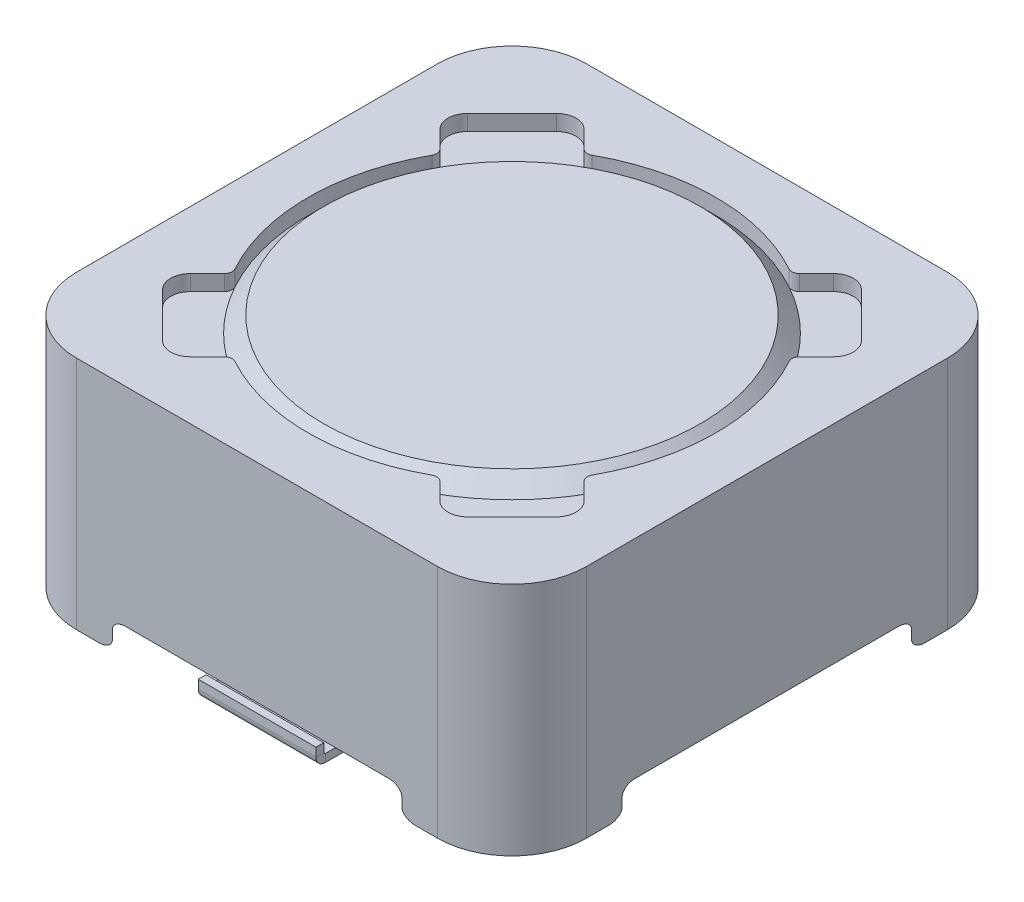
SolidWorks part; units mm, degrees
ref_plane "Front Plane" through (0, 0, 0) normal (0, 0, 1) x (1, 0, 0)
ref_plane "Top Plane" through (0, 0, 0) normal (0, 1, 0) x (1, 0, 0)
ref_plane "Right Plane" through (0, 0, 0) normal (1, 0, 0) x (0, 0, -1)
sketch "Sketch1" plane through (0, 0, 0) normal (0, 1, 0) x (1, 0, 0)
  line L1 (-2.3, 3.25) -> (2.3, 3.25)
  line L2 (-3.25, 2.3) -> (-3.25, -2.3)
  line L3 (-2.3, -3.25) -> (2.3, -3.25)
  line L4 (3.25, 2.3) -> (3.25, -2.3)
  line L5 (-3.25, 3.25) -> (3.25, -3.25) construction
  line L6 (-3.25, -3.25) -> (3.25, 3.25) construction
  arc A0 (3.25, 2.3) -> (2.3, 3.25) centre (2.3, 2.3) ccw
  arc A1 (-2.3, -3.25) -> (-3.25, -2.3) centre (-2.3, -2.3) cw
  arc A2 (2.3, -3.25) -> (3.25, -2.3) centre (2.3, -2.3) ccw
  arc A3 (-2.3, 3.25) -> (-3.25, 2.3) centre (-2.3, 2.3) ccw
  point P0 (0, 0)
  dimension "D1" = 6.5
  dimension "D2" = 6.5
  dimension "D3" = 4.6
extrude "Boss-Extrude1" add sketch "Sketch1" along normal blind 3
sketch "Sketch2" plane through (0, 3, 0) normal (0, 1, 0) x (1, 0, 0)
  line L0 (-1.3744, 2.2937) -> (-1.591, 2.5102)
  line L1 (-1.9445, 2.5102) -> (-2.5102, 1.9445)
  line L2 (-2.5102, 1.591) -> (-2.2937, 1.3744)
  line L3 (0, 0) -> (0, -1.7284) construction
  line L4 (-2.2274, 2.2274) -> (2.2274, -2.2274) construction
  line L5 (1.591, 2.5102) -> (1.3744, 2.2937)
  line L6 (2.5102, 1.9445) -> (1.9445, 2.5102)
  line L7 (2.2937, 1.3744) -> (2.5102, 1.591)
  line L8 (2.5102, -1.591) -> (2.2937, -1.3744)
  line L9 (1.9445, -2.5102) -> (2.5102, -1.9445)
  line L10 (1.3744, -2.2937) -> (1.591, -2.5102)
  line L11 (-1.591, -2.5102) -> (-1.3744, -2.2937)
  line L12 (-2.5102, -1.9445) -> (-1.9445, -2.5102)
  line L13 (-2.2937, -1.3744) -> (-2.5102, -1.591)
  arc A0 (-2.2768, 1.2554) -> (-2.2768, -1.2554) centre (0, 0) ccw
  arc A1 (-2.5102, 1.591) -> (-2.5102, 1.9445) centre (-2.3335, 1.7678) cw
  arc A2 (-1.9445, 2.5102) -> (-1.591, 2.5102) centre (-1.7678, 2.3335) cw
  arc A3 (-2.2768, 1.2554) -> (-2.2937, 1.3744) centre (-2.3644, 1.3037) ccw
  arc A4 (-1.2554, 2.2768) -> (-1.3744, 2.2937) centre (-1.3037, 2.3644) cw
  arc A5 (1.2554, 2.2768) -> (1.3744, 2.2937) centre (1.3037, 2.3644) ccw
  arc A6 (1.591, 2.5102) -> (1.9445, 2.5102) centre (1.7678, 2.3335) cw
  arc A7 (2.5102, 1.9445) -> (2.5102, 1.591) centre (2.3335, 1.7678) cw
  arc A8 (2.2768, 1.2554) -> (2.2937, 1.3744) centre (2.3644, 1.3037) cw
  arc A9 (2.2768, -1.2554) -> (2.2937, -1.3744) centre (2.3644, -1.3037) ccw
  arc A10 (2.5102, -1.591) -> (2.5102, -1.9445) centre (2.3335, -1.7678) cw
  arc A11 (1.9445, -2.5102) -> (1.591, -2.5102) centre (1.7678, -2.3335) cw
  arc A12 (1.2554, -2.2768) -> (1.3744, -2.2937) centre (1.3037, -2.3644) cw
  arc A13 (-1.2554, -2.2768) -> (-1.3744, -2.2937) centre (-1.3037, -2.3644) ccw
  arc A14 (-1.591, -2.5102) -> (-1.9445, -2.5102) centre (-1.7678, -2.3335) cw
  arc A15 (-2.5102, -1.9445) -> (-2.5102, -1.591) centre (-2.3335, -1.7678) cw
  arc A16 (-2.2768, -1.2554) -> (-2.2937, -1.3744) centre (-2.3644, -1.3037) cw
  arc A17 (1.2554, 2.2768) -> (-1.2554, 2.2768) centre (0, 0) ccw
  arc A18 (2.2768, -1.2554) -> (2.2768, 1.2554) centre (0, 0) ccw
  arc A19 (-1.2554, -2.2768) -> (1.2554, -2.2768) centre (0, 0) ccw
  point P1 (1.3037, 2.2937)
  point P5 (-2.2274, 2.2274)
  point P11 (0, 0)
  point P14 (-2.687, 1.7678)
  point P17 (-1.7678, 2.687)
  point P20 (-1.8385, 1.8385)
  point P61 (0, 0)
  dimension "D3" = 0.55
  dimension "D1" = 5.2
  dimension "D5" = 0.25
  dimension "D6" = 0.1
  dimension "D2" = 45
  dimension "D4" = 1.3
  dimension "D7" = 4
extrude "Cut-Extrude1" cut sketch "Sketch2" against normal blind 0.2
sketch "Sketch3" plane through (0, 2.8, 0) normal (0, 1, 0) x (1, 0, 0)
  circle A0 centre (0, 0) radius 2.4
  dimension "D1" = 4.8
extrude "Boss-Extrude2" add sketch "Sketch3" along normal up to surface (0.2 mm away) up to face at (0, 3, 0)
chamfer "Chamfer2" distance 0.2 angle 45 1 edges at (0, 2.8, -2.4)
sketch "Sketch4" plane through (0, 0, 0) normal (0, -1, 0) x (1, 0, 0)
  line L0 (-3.25, 1.845) -> (-1.845, 3.25)
  line L1 (-1.845, 3.25) -> (1.845, 3.25)
  line L2 (1.845, 3.25) -> (3.25, 1.845)
  line L3 (3.25, 1.845) -> (3.25, -1.845)
  line L4 (3.25, -1.845) -> (1.845, -3.25)
  line L5 (1.845, -3.25) -> (-1.845, -3.25)
  line L6 (-1.845, -3.25) -> (-3.25, -1.845)
  line L7 (-3.25, -1.845) -> (-3.25, 1.845)
  line L8 (-3.25, -2.3) -> (-3.25, 2.3) construction
  line L9 (2.3, -3.25) -> (-2.3, -3.25) construction
  line L10 (-2.3, 3.25) -> (2.3, 3.25) construction
  line L11 (3.25, 2.3) -> (3.25, -2.3) construction
  arc A0 (-2.3, 3.25) -> (-3.25, 2.3) centre (-2.3, 2.3) ccw construction
  point P2 (-1.8291, 3.25)
  point P4 (-3.0233, 0.7466)
  point P10 (-2.9718, 2.9718)
  point P12 (-2.5475, 2.5475)
  point P25 (-1.5253, 3.25)
  dimension "D1" = 135
  dimension "D2" = 0.6
extrude "Cut-Extrude2" cut sketch "Sketch4" against normal blind 0.35
fillet "Fillet1" radius 0.12 8 edges at (2.5475, 0.35, -2.5475) (-2.5475, 0.35, -2.5475) (-2.5475, 0.35, 2.5475) (2.5475, 0.35, 2.5475) (2.5475, 0, 2.5475) (2.5475, 0, -2.5475) (-2.5475, 0, -2.5475) (-2.5475, 0, 2.5475)
sketch "Sketch6" plane through (0, 0.35, 0) normal (0, -1, 0) x (1, 0, 0)
  line L0 (2.169, -2.169) -> (-2.169, 2.169) construction
  line L1 (0, 0) -> (0, -1.4859) construction
  line L2 (-2.2937, 1.3744) -> (-2.4518, 1.5326)
  line L3 (-2.4518, 1.8862) -> (-1.8862, 2.4518)
  line L4 (-1.5326, 2.4518) -> (-1.3744, 2.2937)
  line L5 (1.3744, 2.2937) -> (1.5326, 2.4518)
  line L6 (1.8862, 2.4518) -> (2.4518, 1.8862)
  line L7 (2.4518, 1.5326) -> (2.2937, 1.3744)
  line L8 (2.2937, -1.3744) -> (2.4518, -1.5326)
  line L9 (2.4518, -1.8862) -> (1.8862, -2.4518)
  line L10 (1.5326, -2.4518) -> (1.3744, -2.2937)
  line L11 (-1.3744, -2.2937) -> (-1.5326, -2.4518)
  line L12 (-1.8862, -2.4518) -> (-2.4518, -1.8862)
  line L13 (-2.4518, -1.5326) -> (-2.2937, -1.3744)
  arc A0 (-2.2768, 1.2554) -> (-2.2768, -1.2554) centre (0, 0) ccw
  arc A2 (-2.4518, 1.5326) -> (-2.4518, 1.8862) centre (-2.2751, 1.7094) cw
  arc A3 (-1.5326, 2.4518) -> (-1.8862, 2.4518) centre (-1.7094, 2.2751) ccw
  arc A4 (-2.2937, 1.3744) -> (-2.2768, 1.2554) centre (-2.3644, 1.3037) cw
  arc A5 (-1.2554, 2.2768) -> (-1.3744, 2.2937) centre (-1.3037, 2.3644) cw
  arc A6 (1.3744, 2.2937) -> (1.2554, 2.2768) centre (1.3037, 2.3644) cw
  arc A7 (1.5326, 2.4518) -> (1.8862, 2.4518) centre (1.7094, 2.2751) cw
  arc A8 (2.4518, 1.5326) -> (2.4518, 1.8862) centre (2.2751, 1.7094) ccw
  arc A9 (2.2768, 1.2554) -> (2.2937, 1.3744) centre (2.3644, 1.3037) cw
  arc A10 (2.2937, -1.3744) -> (2.2768, -1.2554) centre (2.3644, -1.3037) cw
  arc A11 (2.4518, -1.5326) -> (2.4518, -1.8862) centre (2.2751, -1.7094) cw
  arc A12 (1.5326, -2.4518) -> (1.8862, -2.4518) centre (1.7094, -2.2751) ccw
  arc A13 (1.2554, -2.2768) -> (1.3744, -2.2937) centre (1.3037, -2.3644) cw
  arc A14 (-1.3744, -2.2937) -> (-1.2554, -2.2768) centre (-1.3037, -2.3644) cw
  arc A15 (-1.5326, -2.4518) -> (-1.8862, -2.4518) centre (-1.7094, -2.2751) cw
  arc A16 (-2.4518, -1.5326) -> (-2.4518, -1.8862) centre (-2.2751, -1.7094) ccw
  arc A17 (-2.2768, -1.2554) -> (-2.2937, -1.3744) centre (-2.3644, -1.3037) cw
  arc A18 (1.2554, 2.2768) -> (-1.2554, 2.2768) centre (0, 0) ccw
  arc A19 (2.2768, -1.2554) -> (2.2768, 1.2554) centre (0, 0) ccw
  arc A20 (-1.2554, -2.2768) -> (1.2554, -2.2768) centre (0, 0) ccw
  point P9 (0, 0)
  point P17 (-1.3205, 2.2397)
  point P26 (-1.7094, 2.6286)
  point P62 (0, 0)
  dimension "D4" = 0.25
  dimension "D5" = 0.1
  dimension "D7" = 2.6
  dimension "D1" = 45
  dimension "D2" = 1.3
  dimension "D3" = 0.55
  dimension "D6" = 4
extrude "Cut-Extrude3" cut sketch "Sketch6" against normal blind 0.2
sketch "Sketch7" plane through (0, 0.55, 0) normal (0, -1, 0) x (1, 0, 0)
  circle A0 centre (0, 0) radius 2.3
  dimension "D1" = 4.6
extrude "Boss-Extrude3" add sketch "Sketch7" along normal offset from surface (0.3 mm away) 0.1 up to face at (0, 0.35, 0) offset beyond the face yes
chamfer "Chamfer3" distance 0.3 angle 45 1 edges at (0, 0.55, 2.3)
sketch "Sketch8" plane through (0, 0.25, 0) normal (0, -1, 0) x (1, 0, 0)
  line L0 (-2.3, 0) -> (2.1316, 0.8639)
  circle A0 centre (0, 0) radius 2.3 construction
  arc A1 (2.1316, 0.8639) -> (-2.3, 0) centre (0, 0) ccw
  point P5 (-2.2925, 0.1856)
  point P6 (2.1316, 0.8639)
  point P7 (-2.3, 0)
extrude "Boss-Extrude4" add sketch "Sketch8" along normal blind 0.1
ref_plane "Plane1" through (0, 0, 2.3) normal (0, 0, 1) x (1, 0, 0)
sketch "Sketch9" plane through (0, 0, 0) normal (1, 0, 0) x (0, 0, -1)
  line L0 (-3.13, 0.05) -> (-2.59, 0.05)
  line L1 (-2.45, 0.2) -> (-2.3, 0.2)
  line L2 (-3.2, 0.12) -> (-3.2, 0.23)
  line L3 (-3.25, 0) -> (-2.0147, 0) construction
  line L5 (-2.52, 0.12) -> (-2.52, 0.13)
  line L7 (-3.25, 0.23) -> (-3.25, 0.12) construction
  line L8 (-1.6753, 0.35) -> (-3.25, 0.35) construction
  line L11 (-2.3, 0.15) -> (0, 0.15) construction
  line L12 (-2.3, 0.4397) -> (-2.3, -0.4397) construction
  arc A0 (-2.59, 0.05) -> (-2.52, 0.12) centre (-2.59, 0.12) ccw
  arc A1 (-2.52, 0.13) -> (-2.45, 0.2) centre (-2.45, 0.13) cw
  arc A2 (-3.13, 0.05) -> (-3.2, 0.12) centre (-3.13, 0.12) cw
  point P9 (-3.135, 0.05)
  dimension "D7" = 0.07
  dimension "D3" = 0.05
  dimension "D4" = 0.12
  dimension "D5" = 0.05
  dimension "D2" = 0.15
  dimension "D1" = 0.05
sketch "Sketch10" plane through (0, 0, 2.3) normal (0, 0, 1) x (1, 0, 0)
  line L0 (-2.3, 0.15) -> (2.1316, 0.15) construction
  line L1 (0.75, 0.15) -> (-0.75, 0.15)
  line L2 (0.75, 0.15) -> (0.75, 0.25)
  line L3 (0.75, 0.25) -> (-0.75, 0.25)
  line L4 (-0.75, 0.15) -> (-0.75, 0.25)
  line L5 (0.75, 0.15) -> (-0.75, 0.25) construction
  line L6 (0.75, 0.25) -> (-0.75, 0.15) construction
  line L7 (2.1316, 0.25) -> (-2.3, 0.25) construction
  point P0 (0, 0.2)
  point P9 (0, 0)
  point P11 (0.75, 0.15)
  dimension "D1" = 1.5
sweep "Sweep2" add profiles "Sketch10" path "Sketch9"
sketch "Sketch11" plane through (0, 0, 2.3) normal (0, 0, -1) x (-1, 0, 0)
  line L1 (0.75, 0.15) -> (-0.75, 0.15)
  line L2 (0.75, 0.15) -> (0.75, 0.25)
  line L3 (0.75, 0.25) -> (-0.75, 0.25)
  line L4 (-0.75, 0.15) -> (-0.75, 0.25)
extrude "Boss-Extrude5" add sketch "Sketch11" along normal up to surface (0.1257 mm away) up to face at (-0.2621, 0.2, 1.3447)
sketch "Sketch12" plane through (0, 0, 0) normal (0, 0, 1) x (1, 0, 0)
  line L0 (0, 0) -> (0, 4.3245) construction
pattern_circular "CirPattern1" count 2 over 360 about axis through (0, 0, 0) along (0, 1, 0) of "Boss-Extrude5", "Sweep2", "Boss-Extrude4"
equation "\"A\"=6.5"
equation "\"B\"=6.5"
equation "\"C\"= 3"
equation "\"D\"= 1.5"
equation "\"E\"= 6.6"
equation "\"F\"= 4.6"
equation "\"D1@Sketch1\"=\"A\""
equation "\"D2@Sketch1\"=\"B\""
equation "\"D3@Sketch1\"=\"F\""
equation "\"D1@Boss-Extrude1\"=\"C\""
equation "\"D2@Sketch6\"=\"D4@Sketch2\""
equation "\"D3@Sketch6\"=\"D3@Sketch2\""
equation "\"D4@Sketch6\"=\"D5@Sketch2\""
equation "\"D5@Sketch6\"=\"D6@Sketch2\""
equation "\"D7@Sketch6\"=\"D1@Sketch2\"/2"
equation "\"D1@Sketch7\"=\"D1@Sketch3\"-0.2"
equation "\"t_metal\"= 0.1"
equation "\"D1@Boss-Extrude4\"=\"t_metal\""
equation "\"D3@Sketch9\"=\"t_metal\"/2"
equation "\"D1@Sketch10\"=\"D\""
equation "\"D5@Sketch9\"=\"t_metal\"/2"
equation "\"D1@Sketch9\"=\"t_metal\"/2"
